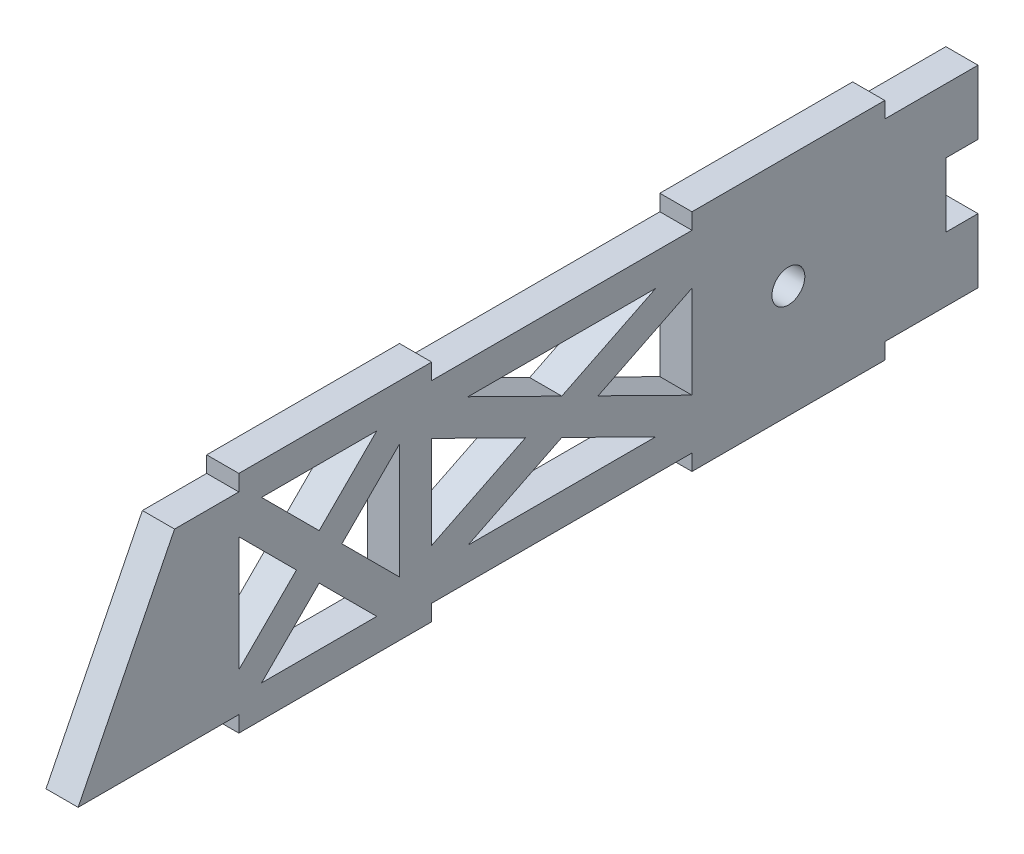
SolidWorks part; units mm, degrees
material "7050-T73510"
ref_plane "Front Plane" through (0, 0, 0) normal (0, 0, 1) x (1, 0, 0)
ref_plane "Top Plane" through (0, 0, 0) normal (0, 1, 0) x (1, 0, 0)
ref_plane "Right Plane" through (0, 0, 0) normal (1, 0, 0) x (0, 0, -1)
sketch "Sketch1" plane through (0, 0, 0) normal (1, 0, 0) x (0, 0, -1)
  line L1 (-177.8, -38.1) -> (177.8, -38.1)
  line L2 (-177.8, -38.1) -> (-177.8, 38.1)
  line L3 (-177.8, 38.1) -> (177.8, 38.1)
  line L4 (177.8, -38.1) -> (177.8, 38.1)
  line L5 (-177.8, -38.1) -> (177.8, 38.1) construction
  line L6 (-177.8, 38.1) -> (177.8, -38.1) construction
  point P0 (0, 0)
  dimension "D1" = 355.6
  dimension "D2" = 76.2
extrude "Boss-Extrude1" add sketch "Sketch1" along normal blind 12.7
sketch "Sketch2" plane through (12.7, 0, 0) normal (1, 0, 0) x (0, 0, -1)
  line L0 (-177.8, -38.1) -> (-139.7, 38.1)
  line L1 (177.8, 38.1) -> (-177.8, 38.1) construction
  dimension "D1" = 38.1
extrude "Cut-Extrude1" cut sketch "Sketch2" against normal through all and the other way through all
sketch "Sketch3" plane through (0, 0, 0) normal (-1, 0, 0) x (0, 0, 1)
  line L0 (177.8, -38.1) -> (-177.8, -38.1) construction
  line L1 (-140.97, -38.1) -> (-64.77, -38.1)
  line L2 (-140.97, -38.1) -> (-140.97, -44.45)
  line L3 (-140.97, -44.45) -> (-64.77, -44.45)
  line L4 (-64.77, -38.1) -> (-64.77, -44.45)
  line L5 (-177.8, -38.1) -> (-177.8, 38.1) construction
  line L6 (38.1, -38.1) -> (114.3, -38.1)
  line L7 (38.1, -38.1) -> (38.1, -44.45)
  line L8 (38.1, -44.45) -> (114.3, -44.45)
  line L9 (114.3, -38.1) -> (114.3, -44.45)
  line L10 (-177.8, 38.1) -> (139.7, 38.1) construction
  line L11 (-140.97, 38.1) -> (-64.77, 38.1)
  line L12 (-140.97, 38.1) -> (-140.97, 44.45)
  line L13 (-140.97, 44.45) -> (-64.77, 44.45)
  line L14 (-64.77, 38.1) -> (-64.77, 44.45)
  line L16 (38.1, 38.1) -> (114.3, 38.1)
  line L17 (38.1, 38.1) -> (38.1, 44.45)
  line L18 (38.1, 44.45) -> (114.3, 44.45)
  line L19 (114.3, 38.1) -> (114.3, 44.45)
  dimension "D1" = 76.2
  dimension "D2" = 6.35
  dimension "D3" = 76.2
  dimension "D4" = 6.35
  dimension "D5" = 36.83
  dimension "D6" = 215.9
  dimension "D7" = 76.2
  dimension "D8" = 6.35
  dimension "D9" = 6.35
  dimension "D10" = 76.2
extrude "Boss-Extrude2" add sketch "Sketch3" against normal blind 12.7
sketch "Sketch4" plane through (0, 0, 0) normal (-1, 0, 0) x (0, 0, 1)
  line L0 (-177.8, -38.1) -> (-177.8, 38.1) construction
  line L1 (-177.8, 12.7) -> (-165.1, 12.7)
  line L2 (-177.8, 12.7) -> (-177.8, -12.7)
  line L3 (-177.8, -12.7) -> (-165.1, -12.7)
  line L4 (-165.1, 12.7) -> (-165.1, -12.7)
  line L5 (-140.97, -38.1) -> (-177.8, -38.1) construction
  line L6 (-177.8, 38.1) -> (-140.97, 38.1) construction
  dimension "D1" = 25.4
  dimension "D2" = 25.4
  dimension "D3" = 12.7
extrude "Cut-Extrude2" cut sketch "Sketch4" against normal through all
sketch "Sketch5" plane through (0, 0, 0) normal (-1, 0, 0) x (0, 0, 1)
  line L0 (-165.1, -12.7) -> (-165.1, 12.7) construction
  line L1 (-140.97, -38.1) -> (-177.8, -38.1) construction
  circle A0 centre (-102.87, 0) radius 6.5
  dimension "D1" = 62.23
  dimension "D3" = 13
  dimension "D2" = 38.1
extrude "Cut-Extrude3" cut sketch "Sketch5" against normal through all
sketch "Sketch6" plane through (0, 0, 0) normal (-1, 0, 0) x (0, 0, 1)
  line L0 (38.1, -38.1) -> (-64.77, -38.1) construction
  line L1 (-64.77, 25.4) -> (38.1, 25.4)
  line L2 (-64.77, 25.4) -> (-64.77, -25.4)
  line L3 (-64.77, -25.4) -> (38.1, -25.4)
  line L4 (38.1, 25.4) -> (38.1, -25.4)
  line L5 (-64.77, 38.1) -> (38.1, 38.1) construction
  line L6 (38.1, 44.45) -> (38.1, 38.1) construction
  line L7 (-64.77, 38.1) -> (-64.77, 44.45) construction
  line L8 (-64.77, 25.4) -> (38.1, -25.4) construction
  line L9 (-64.77, -25.4) -> (38.1, 25.4) construction
  line L10 (-50.4288, -25.4) -> (-13.335, -7.0821)
  line L11 (23.7588, 25.4) -> (-13.335, 7.0821)
  line L12 (-50.4288, 25.4) -> (-13.335, 7.0821)
  line L13 (23.7588, -25.4) -> (-13.335, -7.0821)
  line L14 (1.0062, 0) -> (38.1, 18.3179)
  line L15 (-27.6762, 0) -> (-64.77, 18.3179)
  line L16 (1.0062, 0) -> (38.1, -18.3179)
  line L17 (-27.6762, 0) -> (-64.77, -18.3179)
  line L18 (38.1, -44.45) -> (114.3, -44.45) construction
  line L19 (50.8, 31.75) -> (114.3, 31.75)
  line L20 (50.8, 31.75) -> (50.8, -31.75)
  line L21 (50.8, -31.75) -> (114.3, -31.75)
  line L22 (114.3, 31.75) -> (114.3, -31.75)
  line L23 (114.3, 44.45) -> (38.1, 44.45) construction
  line L26 (114.3, 38.1) -> (114.3, 44.45) construction
  line L28 (50.8, -31.75) -> (114.3, 31.75) construction
  line L29 (114.3, -31.75) -> (50.8, 31.75) construction
  line L30 (59.7803, -31.75) -> (114.3, 22.7697)
  line L31 (50.8, -22.7697) -> (105.3197, 31.75)
  line L32 (114.3, -22.7697) -> (59.7803, 31.75)
  line L33 (105.3197, -31.75) -> (50.8, 22.7697)
  point P36 (114.3, 41.275)
  dimension "D1" = 12.7
  dimension "D2" = 12.7
  dimension "D3" = 12.7
  dimension "D4" = 12.7
  dimension "D5" = 12.7
  dimension "D6" = 12.7
  dimension "D7" = 12.7
  dimension "D8" = 0
  dimension "D9" = 12.7
  dimension "D10" = 12.7
extrude "Cut-Extrude4" cut sketch "Sketch6" against normal through all contours L3 L13 L10 | L17 L15 L2 | L1 L12 L11 | L14 L16 L4 | L21 L33 L30 | L32 L22 L30 | L31 L33 L20 | L32 L31 L19 region at (0, 19.294, -13.335) region at (0, 0, -52.4054) region at (0, 0, 25.7354) region at (0, -19.294, -13.335) region at (0, 24.1601, 82.55) region at (0, 0, 58.3899) region at (0, 0, 106.7101) region at (0, -24.1601, 82.55)
